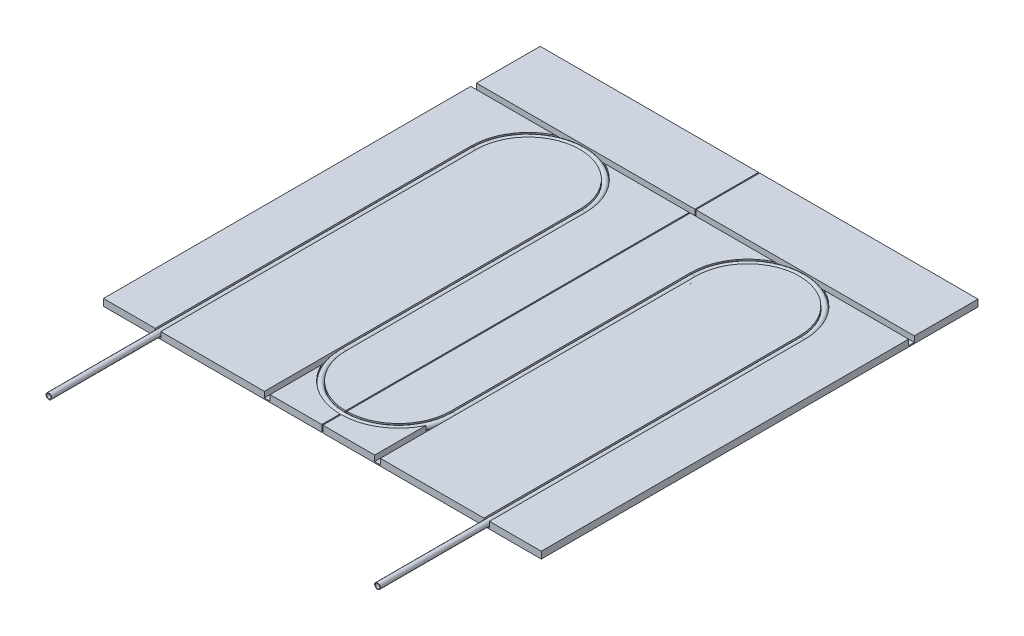
SolidWorks part; units mm, degrees
material "Cedar"
ref_plane "Front" through (0, 0, 0) normal (0, 0, 1) x (1, 0, 0)
ref_plane "Top" through (0, 0, 0) normal (0, 1, 0) x (1, 0, 0)
ref_plane "Right" through (0, 0, 0) normal (1, 0, 0) x (0, 0, -1)
sketch "Sketch1" plane through (0, 0, 0) normal (0, 1, 0) x (1, 0, 0)
  line L0 (-306.3875, 0) -> (306.3875, 0) construction
  line L2 (-1.5875, 609.6) -> (-611.1875, 609.6)
  line L3 (-1.5875, 609.6) -> (-1.5875, -609.6)
  line L4 (-1.5875, -609.6) -> (-611.1875, -609.6)
  line L5 (-611.1875, 609.6) -> (-611.1875, -609.6)
  line L6 (-1.5875, 609.6) -> (-611.1875, -609.6) construction
  line L7 (-1.5875, -609.6) -> (-611.1875, 609.6) construction
  line L8 (1.5875, 609.6) -> (611.1875, 609.6) construction
  line L9 (1.5875, 609.6) -> (1.5875, -609.6) construction
  line L10 (1.5875, -609.6) -> (611.1875, -609.6) construction
  line L11 (611.1875, 609.6) -> (611.1875, -609.6) construction
  line L12 (1.5875, 609.6) -> (611.1875, -609.6) construction
  line L13 (1.5875, -609.6) -> (611.1875, 609.6) construction
  point P2 (0, 0)
  dimension "D1" = 612.775
  dimension "D2" = 609.6
  dimension "D3" = 1219.2
extrude "Boss-Extrude1" add sketch "Sketch1" along normal blind 19.05
sketch "Sketch2" plane through (0, 19.05, 0) normal (0, 1, 0) x (1, 0, 0)
  line L0 (-611.1875, -609.6) -> (-1.5875, -609.6) construction
  line L1 (-466.725, -609.6) -> (-450.85, -609.6)
  line L2 (-466.725, -609.6) -> (-466.725, 271.4625)
  line L3 (-466.725, 271.4625) -> (-450.85, 271.4625) construction
  line L4 (-450.85, -609.6) -> (-450.85, 271.4625)
  line L5 (-450.85, -169.0688) -> (-161.925, -169.0688) construction
  line L6 (-146.05, -609.6) -> (-161.925, -609.6)
  line L7 (-146.05, -609.6) -> (-146.05, 271.4625)
  line L8 (-146.05, 271.4625) -> (-161.925, 271.4625) construction
  line L9 (-161.925, -609.6) -> (-161.925, 271.4625)
  line L10 (-466.725, -169.0688) -> (-611.1875, -169.0688) construction
  line L11 (-611.1875, 609.6) -> (-611.1875, -609.6) construction
  line L12 (-146.05, -169.0688) -> (-1.5875, -169.0688) construction
  line L13 (-458.7875, -609.6) -> (-458.7875, 271.4625) construction
  line L14 (-1.5875, -609.6) -> (-1.5875, 609.6) construction
  line L15 (-450.85, 271.4625) -> (-161.925, 271.4625) construction
  line L16 (-153.9875, 271.4625) -> (-153.9875, -609.6) construction
  line L18 (-1.5875, 609.6) -> (-611.1875, 609.6) construction
  arc A0 (-161.925, 271.4625) -> (-450.85, 271.4625) centre (-306.3875, 271.4625) ccw
  arc A1 (-146.05, 271.4625) -> (-466.725, 271.4625) centre (-306.3875, 271.4625) ccw
  dimension "D3" = 177.8
  dimension "D1" = 304.8
  dimension "D2" = 15.875
extrude "Cut-Extrude1" cut sketch "Sketch2" against normal blind 15.875
sketch "Sketch3" plane through (0, 19.05, 0) normal (0, 1, 0) x (1, 0, 0)
  line L0 (-1.5875, -609.6) -> (-1.5875, 609.6) construction
  line L1 (-611.1875, 431.8) -> (-1.5875, 431.8)
  line L2 (-611.1875, 431.8) -> (-611.1875, 415.925)
  line L3 (-611.1875, 415.925) -> (-1.5875, 415.925)
  line L4 (-1.5875, 431.8) -> (-1.5875, 415.925)
  line L5 (-611.1875, 431.8) -> (-1.5875, 415.925) construction
  line L6 (-611.1875, 415.925) -> (-1.5875, 431.8) construction
  line L7 (-611.1875, 609.6) -> (-611.1875, -609.6) construction
  line L8 (-466.725, -609.6) -> (-450.85, -609.6) construction
  arc A0 (-146.05, 271.4625) -> (-466.725, 271.4625) centre (-306.3875, 271.4625) ccw construction
  point P0 (-306.3875, 423.8625)
extrude "Cut-Extrude2" cut sketch "Sketch3" against normal up to surface (15.875 mm away) up to face at (-306.3875, 3.175, 130.9688)
mirror "Mirror3" about plane through (0, 0, 0) normal (1, 0, 0) of bodies 182
sketch "Sketch5" plane through (0, 19.05, 0) normal (0, 1, 0) x (1, 0, 0)
  line L0 (0, 0) -> (0, -609.6) construction
  line L1 (0, -609.6) -> (-1.5875, -609.6) construction
  line L2 (-146.05, -609.6) -> (-1.5875, -609.6) construction
  line L3 (146.05, -396.875) -> (161.925, -396.875) construction
  line L4 (-161.925, 271.4625) -> (-161.925, -609.6) construction
  line L5 (-161.925, -396.875) -> (-146.05, -396.875)
  line L6 (146.05, -396.875) -> (161.925, -396.875)
  line L7 (-161.925, 271.4625) -> (-161.925, -609.6) construction
  line L8 (-153.9875, -396.875) -> (153.9875, -396.875) construction
  line L10 (146.05, -609.6) -> (1.5875, -609.6) construction
  arc A0 (-161.925, -396.875) -> (161.925, -396.875) centre (0, -396.875) ccw
  arc A1 (-146.05, -396.875) -> (146.05, -396.875) centre (0, -396.875) ccw
  dimension "D2" = 50.8
  dimension "D1" = 15.875
  dimension "D3" = 307.975
extrude "Cut-Extrude3" cut sketch "Sketch5" against normal up to surface (15.875 mm away) up to face at (-306.3875, 3.175, -96.0976)
sketch "Sketch6" plane through (0, 0, 609.6) normal (0, 0, 1) x (1, 0, 0)
  line L0 (-466.725, 19.05) -> (-450.85, 3.175) construction
  circle A0 centre (-458.7875, 11.1125) radius 7.9375
  circle A1 centre (-458.7875, 11.1125) radius 6.35
  dimension "D1" = 15.875
  dimension "D2" = 12.7
ref_plane "Plane1" through (0, 11.1125, 0) normal (0, 1, 0) x (1, 0, 0)
sketch "Sketch7" plane through (0, 11.1125, 0) normal (0, 1, 0) x (1, 0, 0)
  line L0 (-450.85, -609.6) -> (-450.85, 271.4625) construction
  line L1 (-153.9875, 271.4625) -> (-153.9875, -396.875)
  line L2 (-161.925, 271.4625) -> (-161.925, -609.6) construction
  line L3 (-161.925, 271.4625) -> (-161.925, -609.6) construction
  line L4 (-450.85, -609.6) -> (-450.85, 271.4625) construction
  line L5 (450.85, -609.6) -> (450.85, 271.4625) construction
  line L6 (450.85, -609.6) -> (450.85, 271.4625) construction
  line L7 (161.925, 271.4625) -> (161.925, -609.6) construction
  line L8 (161.925, 271.4625) -> (161.925, -609.6) construction
  line L9 (-153.9875, 271.4625) -> (-153.9875, -609.6) construction
  line L10 (153.9875, 271.4625) -> (153.9875, -609.6) construction
  line L12 (-458.7875, -609.6) -> (-458.7875, 271.4625)
  line L13 (458.7875, -609.6) -> (458.7875, 271.4625)
  line L14 (153.9875, 271.4625) -> (153.9875, -396.875)
  line L15 (-1.5875, -609.6) -> (1.5875, -609.6) construction
  line L16 (-1.5875, -609.6) -> (-1.5875, -558.7922) construction
  line L17 (1.5875, -609.6) -> (1.5875, -558.7922) construction
  line L18 (0, -609.6) -> (0, -396.875) construction
  arc A0 (-161.925, 271.4625) -> (-450.85, 271.4625) centre (-306.3875, 271.4625) ccw construction
  arc A1 (-161.925, 271.4625) -> (-450.85, 271.4625) centre (-306.3875, 271.4625) ccw construction
  arc A2 (450.85, 271.4625) -> (161.925, 271.4625) centre (306.3875, 271.4625) ccw construction
  arc A3 (450.85, 271.4625) -> (161.925, 271.4625) centre (306.3875, 271.4625) ccw construction
  arc A5 (-153.9875, 271.4625) -> (-458.7875, 271.4625) centre (-306.3875, 271.4625) ccw
  arc A6 (458.7875, 271.4625) -> (153.9875, 271.4625) centre (306.3875, 271.4625) ccw
  arc A7 (-153.9875, -396.875) -> (153.9875, -396.875) centre (0, -396.875) ccw
  arc A8 (-146.05, -396.875) -> (-1.5875, -542.9164) centre (0, -396.875) ccw construction
  dimension "D1" = 7.9375
sweep "Sweep1" add profiles "Sketch6" path "Sketch7"
sketch "Sketch8" plane through (0, 0, 609.6) normal (0, 0, 1) x (1, 0, 0)
  circle A0 centre (-458.7875, 11.1125) radius 6.35 construction
  circle A1 centre (-458.7875, 11.1125) radius 7.9375
  circle A2 centre (-458.7875, 11.1125) radius 7.9375
  circle A3 centre (-458.7875, 11.1125) radius 6.35
  circle A4 centre (458.7875, 11.1125) radius 6.35 construction
  circle A5 centre (458.7875, 11.1125) radius 7.9375
  circle A6 centre (458.7875, 11.1125) radius 7.9375
  circle A7 centre (458.7875, 11.1125) radius 6.35
  dimension "D1" = 0
  dimension "D2" = 0
extrude "Boss-Extrude2" add sketch "Sketch8" along normal blind 304.8
